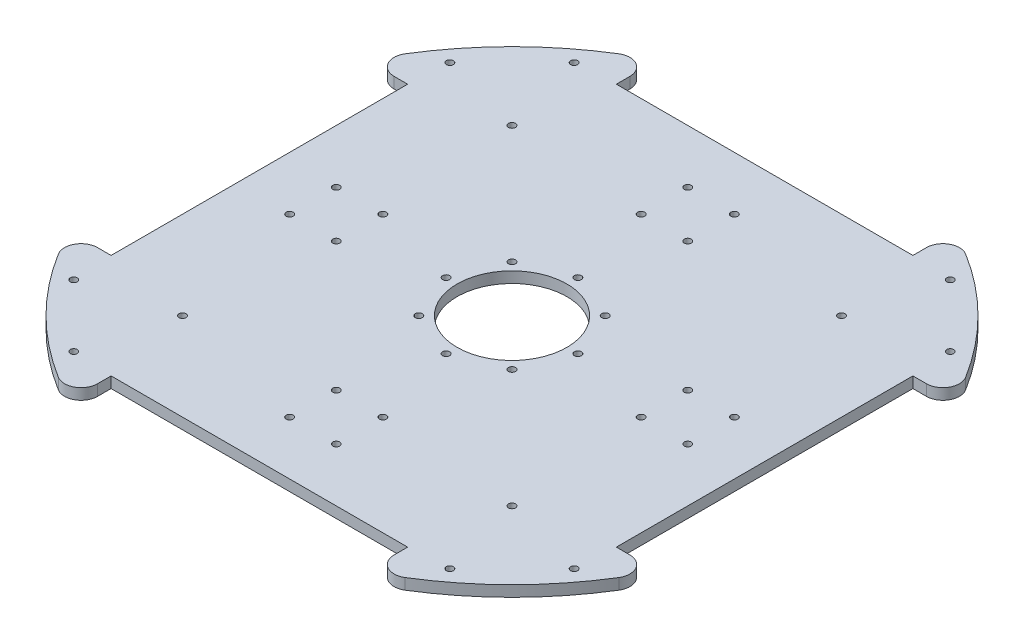
SolidWorks part; units mm, degrees
ref_plane "Front Plane" through (0, 0, 0) normal (0, 0, 1) x (1, 0, 0)
ref_plane "Top Plane" through (0, 0, 0) normal (0, 1, 0) x (1, 0, 0)
ref_plane "Right Plane" through (0, 0, 0) normal (1, 0, 0) x (0, 0, -1)
sketch "Sketch1" plane through (0, 0, 0) normal (0, 1, 0) x (1, 0, 0)
  line L0 (160, 67.5) -> (115, 67.5)
  line L5 (-67.5, 160) -> (67.5, 160)
  line L6 (-67.5, 160) -> (-67.5, 115)
  line L7 (-67.5, 115) -> (67.5, 115)
  line L8 (67.5, 160) -> (67.5, 115)
  line L9 (160, 67.5) -> (160, -67.5)
  line L10 (160, -67.5) -> (115, -67.5)
  line L11 (115, 67.5) -> (115, -67.5)
  line L12 (67.5, -160) -> (67.5, -115)
  line L13 (67.5, -160) -> (-67.5, -160)
  line L14 (-67.5, -160) -> (-67.5, -115)
  line L15 (67.5, -115) -> (-67.5, -115)
  line L16 (-160, -67.5) -> (-115, -67.5)
  line L17 (-160, -67.5) -> (-160, 67.5)
  line L18 (-160, 67.5) -> (-115, 67.5)
  line L19 (-115, -67.5) -> (-115, 67.5)
  line L20 (0, 150) -> (0, 115) construction
  line L21 (0, 160) -> (0, 150) construction
  circle A0 centre (0, 0) radius 150
  point P7 (0, 115)
  point P23 (0, 0)
  dimension "D1" = 300
  dimension "D4" = 35
  dimension "D2" = 135
  dimension "D5" = 10
  dimension "D3" = 4
extrude "Boss-Extrude1" add sketch "Sketch1" along normal blind 5 contours L12 A0 L10 L11 L0 L8 L7 L6 L18 L19 L16 L14 L15 region at (0, 0, 0)
fillet "Fillet1" radius 7.5 8 edges at (-133.9543, 2.5, 67.5) (-133.9543, 2.5, -67.5) (-67.5, 2.5, -133.9543) (67.5, 2.5, -133.9543) (133.9543, 2.5, -67.5) (133.9543, 2.5, 67.5) (67.5, 2.5, 133.9543) (-67.5, 2.5, 133.9543)
sketch "Sketch3" plane through (0, 5, 0) normal (0, 1, 0) x (1, 0, 0)
  line L0 (0, -115) -> (0, -80) construction
  line L1 (67.5, -115) -> (-67.5, -115) construction
  line L2 (-10.6066, -90.6066) -> (10.6066, -90.6066) construction
  line L3 (-115, 0) -> (-80, 0) construction
  line L4 (-90.6066, 10.6066) -> (-90.6066, -10.6066) construction
  line L5 (0, 115) -> (0, 80) construction
  line L6 (10.6066, 90.6066) -> (-10.6066, 90.6066) construction
  line L7 (115, 0) -> (80, 0) construction
  line L8 (90.6066, -10.6066) -> (90.6066, 10.6066) construction
  line L9 (-115, -67.5) -> (-115, 67.5) construction
  circle A0 centre (-10.6066, -90.6066) radius 1.6
  circle A1 centre (-10.6066, -69.3934) radius 1.6
  circle A2 centre (10.6066, -69.3934) radius 1.6
  circle A3 centre (10.6066, -90.6066) radius 1.6
  circle A4 centre (-69.3934, 10.6066) radius 1.6
  circle A5 centre (-69.3934, -10.6066) radius 1.6
  circle A6 centre (-90.6066, -10.6066) radius 1.6
  circle A7 centre (-90.6066, 10.6066) radius 1.6
  circle A8 centre (10.6066, 69.3934) radius 1.6
  circle A9 centre (-10.6066, 69.3934) radius 1.6
  circle A10 centre (-10.6066, 90.6066) radius 1.6
  circle A11 centre (10.6066, 90.6066) radius 1.6
  circle A12 centre (69.3934, -10.6066) radius 1.6
  circle A13 centre (69.3934, 10.6066) radius 1.6
  circle A14 centre (90.6066, 10.6066) radius 1.6
  circle A15 centre (90.6066, -10.6066) radius 1.6
  point P7 (0, -90.6066)
  point P16 (0, -80)
  point P48 (0, 0)
  dimension "D1" = 3.2
  dimension "D2" = 15
  dimension "D3" = 35
  dimension "D4" = 4
  dimension "D5" = 4
extrude "Cut-Extrude2" cut sketch "Sketch3" against normal through all both and the other way through all
sketch "Sketch4" plane through (0, 5, 0) normal (0, 1, 0) x (1, 0, 0)
  circle A0 centre (0, 0) radius 25
  circle A1 centre (0, 30) radius 1.6
  circle A2 centre (21.2132, 21.2132) radius 1.6
  circle A3 centre (30, 0) radius 1.6
  circle A4 centre (21.2132, -21.2132) radius 1.6
  circle A5 centre (0, -30) radius 1.6
  circle A6 centre (-21.2132, -21.2132) radius 1.6
  circle A7 centre (-30, 0) radius 1.6
  circle A8 centre (-21.2132, 21.2132) radius 1.6
  point P22 (0, 0)
  dimension "D1" = 50
  dimension "D2" = 3.2
  dimension "D3" = 30
  dimension "D4" = 8
extrude "Cut-Extrude3" cut sketch "Sketch4" against normal through all both and the other way through all
sketch "Sketch5" plane through (0, 5, 0) normal (0, 1, 0) x (1, 0, 0)
  line L0 (75, -75) -> (106.066, -106.066) construction
  line L1 (-75, -75) -> (-106.066, -106.066) construction
  line L2 (-115, 0) -> (115, 0) construction
  line L3 (-115, -67.5) -> (-115, 67.5) construction
  line L4 (115, 67.5) -> (115, -67.5) construction
  circle A0 centre (75, -75) radius 1.6
  circle A1 centre (-75, -75) radius 1.6
  arc A2 (78.9474, -127.5434) -> (127.5434, -78.9474) centre (0, 0) ccw construction
  arc A3 (-127.5434, -78.9474) -> (-78.9474, -127.5434) centre (0, 0) ccw construction
  circle A9 centre (75, 75) radius 1.6
  circle A10 centre (-75, 75) radius 1.6
  dimension "D1" = 3.2
  dimension "D2" = 150
extrude "Cut-Extrude4" cut sketch "Sketch5" against normal through all both and the other way through all
sketch "Sketch6" plane through (0, 5, 0) normal (0, 1, 0) x (1, 0, 0)
  line L0 (0, 0) -> (-106.066, -106.066) construction
  line L1 (0, 0) -> (-106.066, 106.066) construction
  line L3 (-75, 75) -> (-88.3393, 61.6607) construction
  line L5 (-75, -75) -> (-65.1472, -84.8528) construction
  arc A0 (-127.5434, -78.9474) -> (-78.9474, -127.5434) centre (0, 0) ccw construction
  circle A1 centre (-113.8909, -85.6066) radius 1.6
  circle A3 centre (-85.6066, -113.8909) radius 1.6
  arc A11 (-78.9474, 127.5434) -> (-127.5434, 78.9474) centre (0, 0) ccw construction
  circle A18 centre (-113.8909, 85.6066) radius 1.6
  circle A19 centre (-85.6066, 113.8909) radius 1.6
  circle A20 centre (85.6066, 113.8909) radius 1.6
  circle A21 centre (113.8909, 85.6066) radius 1.6
  circle A22 centre (113.8909, -85.6066) radius 1.6
  circle A23 centre (85.6066, -113.8909) radius 1.6
  point P25 (0, 0)
  point P31 (0, -0.7538)
  point P33 (0, 0)
  dimension "D1" = 3.2
  dimension "D2" = 40
  dimension "D3" = 35
  dimension "D5" = 35
  dimension "D4" = 4
extrude "Cut-Extrude5" cut sketch "Sketch6" against normal through all both and the other way through all
